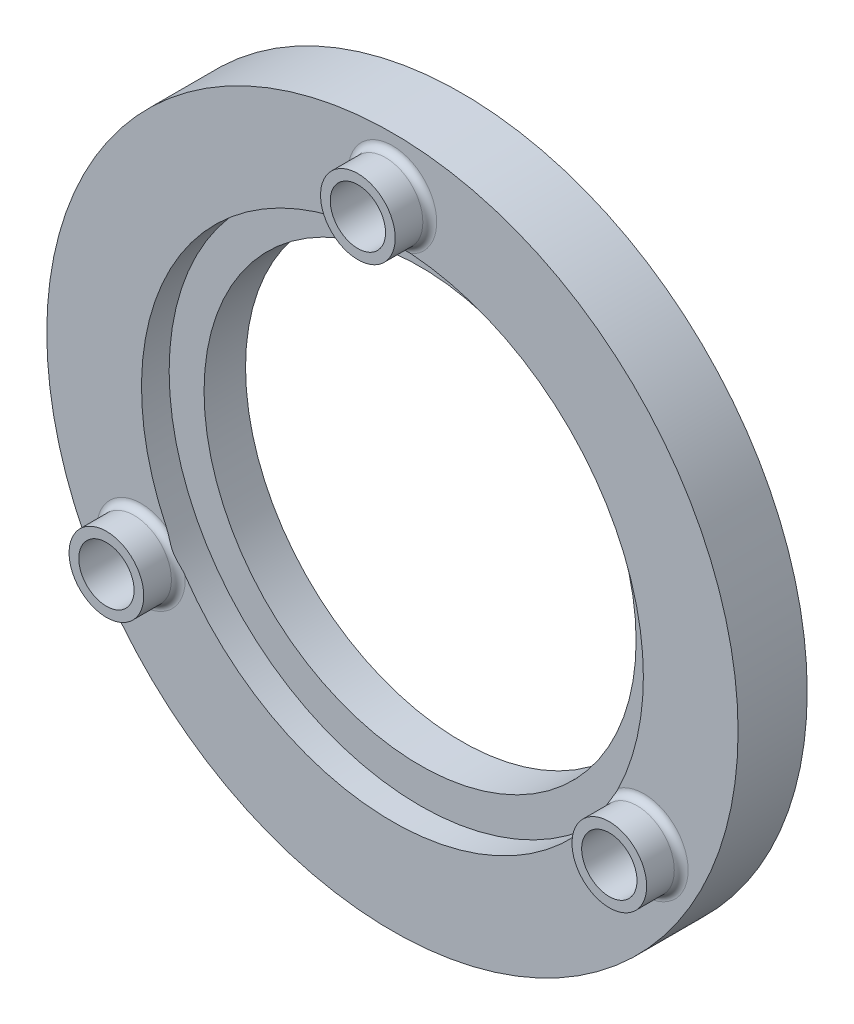
SolidWorks part; units mm, degrees
ref_plane "Front Plane" through (0, 0, 0) normal (0, 0, 1) x (1, 0, 0)
ref_plane "Top Plane" through (0, 0, 0) normal (0, 1, 0) x (1, 0, 0)
ref_plane "Right Plane" through (0, 0, 0) normal (1, 0, 0) x (0, 0, -1)
sketch "Sketch1" plane through (0, 0, 0) normal (0, 0, 1) x (1, 0, 0)
  circle A0 centre (0, 0) radius 25
  circle A1 centre (0, 0) radius 15.625
  dimension "D1" = 50
  dimension "D2" = 31.25
extrude "Boss-Extrude1" add sketch "Sketch1" along normal blind 5
sketch "Sketch2" plane through (0, 0, 5) normal (0, 0, 1) x (1, 0, 0)
  circle A0 centre (0, 0) radius 18.15
  dimension "D1" = 36.3
extrude "Cut-Extrude1" cut sketch "Sketch2" against normal blind 2
sketch "Sketch3" plane through (0, 0, 5) normal (0, 0, 1) x (1, 0, 0)
  circle A0 centre (0, 21) radius 2
  circle A1 centre (-18.1865, -10.5) radius 2
  circle A2 centre (18.1865, -10.5) radius 2
  dimension "D1" = 4
  dimension "D3" = 4
  dimension "D5" = 4
  dimension "D2" = 21
  dimension "D4" = 21
  dimension "D6" = 36.3731
  dimension "D7" = 36.3731
  dimension "D8" = 36.3731
extrude "Cut-Extrude2" cut sketch "Sketch3" against normal blind 5
sketch "Sketch4" plane through (0, 0, 0) normal (0, 0, -1) x (-1, 0, 0)
  line L0 (0, 0) -> (-18.1865, 10.5) construction
  line L1 (3.4641, 21) -> (1.7321, 24)
  line L2 (1.7321, 24) -> (-1.7321, 24)
  line L3 (-1.7321, 24) -> (-3.4641, 21)
  line L4 (-3.4641, 21) -> (-1.7321, 18)
  line L5 (-1.7321, 18) -> (1.7321, 18)
  line L6 (1.7321, 18) -> (3.4641, 21)
  line L7 (-16.4545, -13.5) -> (-19.9186, -13.5)
  line L8 (-14.7224, -10.5) -> (-16.4545, -13.5)
  line L9 (-16.4545, -7.5) -> (-14.7224, -10.5)
  line L10 (-19.9186, -7.5) -> (-16.4545, -7.5)
  line L11 (-21.6506, -10.5) -> (-19.9186, -7.5)
  line L12 (-19.9186, -13.5) -> (-21.6506, -10.5)
  line L13 (0, 0) -> (0, -21) construction
  line L14 (19.9186, -13.5) -> (21.6506, -10.5)
  line L15 (21.6506, -10.5) -> (19.9186, -7.5)
  line L16 (19.9186, -7.5) -> (16.4545, -7.5)
  line L17 (16.4545, -7.5) -> (14.7224, -10.5)
  line L18 (14.7224, -10.5) -> (16.4545, -13.5)
  line L19 (16.4545, -13.5) -> (19.9186, -13.5)
  circle A0 centre (0, 21) radius 3 construction
  dimension "D1" = 6
extrude "Cut-Extrude3" cut sketch "Sketch4" against normal blind 2.7
sketch "Sketch5" plane through (0, 0, 5) normal (0, 0, 1) x (1, 0, 0)
  circle A0 centre (0, 21) radius 2.7
  circle A1 centre (-18.1865, -10.5) radius 2.7
  circle A2 centre (18.1865, -10.5) radius 2.7
  circle A3 centre (-18.1865, -10.5) radius 2
  circle A4 centre (0, 21) radius 2
  circle A5 centre (18.1865, -10.5) radius 2
  dimension "D1" = 5.4
  dimension "D2" = 5.4
  dimension "D3" = 5.4
extrude "Boss-Extrude2" add sketch "Sketch5" along normal blind 2.5
fillet "Fillet1" radius 0.5 1 edges at (-15.4865, -10.5, 5) type face fillet first side face at (-15.4865, -10.5, 7.5) second side face at (-15.4865, -10.5, 5)
fillet "Fillet2" radius 0.5 1 edges at (20.8865, -10.5, 5) type face fillet first side face at (20.8865, -10.5, 7.5) second side face at (25, 0, 5)
fillet "Fillet3" radius 0.5 1 edges at (2.7, 21, 5) type face fillet first side face at (2.7, 21, 7.5) second side face at (25, 0, 5)
